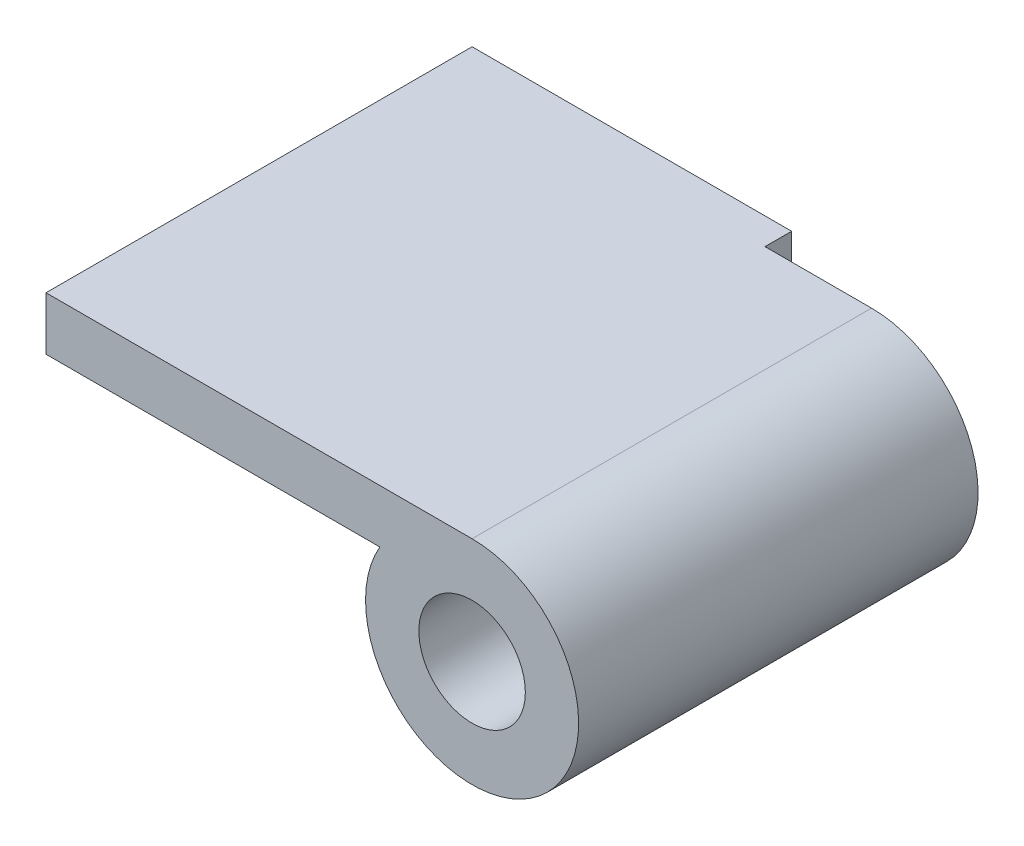
SolidWorks part; units mm, degrees
ref_plane "Front Plane" through (0, 0, 0) normal (0, 0, 1) x (1, 0, 0)
ref_plane "Top Plane" through (0, 0, 0) normal (0, 1, 0) x (1, 0, 0)
ref_plane "Right Plane" through (0, 0, 0) normal (1, 0, 0) x (0, 0, -1)
sketch "Sketch1" plane through (0, 0, 0) normal (0, 0, 1) x (1, 0, 0)
  line L1 (0, 3.175) -> (-25.4, 3.175)
  line L2 (-25.4, 3.175) -> (-25.4, 6.35)
  line L3 (-25.4, 6.35) -> (0, 6.35)
  circle A0 centre (0, 0) radius 6.35
  circle A1 centre (0, 0) radius 3.175
  dimension "D1" = 6.35
  dimension "D2" = 12.7
  dimension "D3" = 25.4
extrude "Boss-Extrude1" add sketch "Sketch1" along normal blind 25.4 contours A0 L3 L2 L1 | A1 A0 region at (-3.0852, 5.3437, 0) region at (-14.613, 4.8143, 0)
sketch "Sketch2" plane through (0, 0, 25.4) normal (0, 0, 1) x (1, 0, 0)
  line L0 (-25.4, 6.35) -> (0, 6.35) construction
  line L1 (6.35, -6.35) -> (-6.35, -6.35)
  line L2 (6.35, -6.35) -> (6.35, 6.35)
  line L3 (6.35, 6.35) -> (-6.35, 6.35)
  line L4 (-6.35, -6.35) -> (-6.35, 6.35)
  line L5 (6.35, -6.35) -> (-6.35, 6.35) construction
  line L6 (6.35, 6.35) -> (-6.35, -6.35) construction
  arc A0 (-5.4993, 3.175) -> (0, 6.35) centre (0, 0) ccw construction
  point P0 (0, 0)
extrude "Cut-Extrude1" cut sketch "Sketch2" along normal blind 1.5875 from surface starting at face at (-12.5937, 2.1971, 0)
